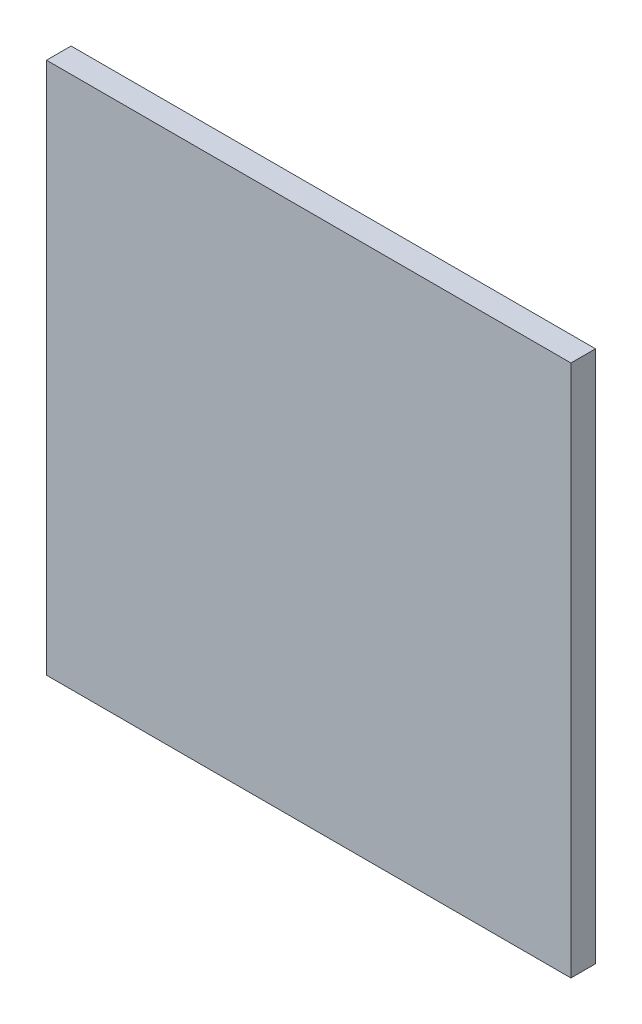
SolidWorks part; units mm, degrees
material "Perspex (TM) GS Acrylic Cast Sheet"
ref_plane "Front Plane" through (0, 0, 0) normal (0, 0, 1) x (1, 0, 0)
ref_plane "Top Plane" through (0, 0, 0) normal (0, 1, 0) x (1, 0, 0)
ref_plane "Right Plane" through (0, 0, 0) normal (1, 0, 0) x (0, 0, -1)
sketch "Sketch1" plane through (0, 0, 0) normal (0, 0, 1) x (1, 0, 0)
  line L1 (-32, -32.5) -> (32, -32.5)
  line L2 (-32, -32.5) -> (-32, 32.5)
  line L3 (-32, 32.5) -> (32, 32.5)
  line L4 (32, -32.5) -> (32, 32.5)
  line L5 (-32, -32.5) -> (32, 32.5) construction
  line L6 (-32, 32.5) -> (32, -32.5) construction
  point P0 (0, 0)
  dimension "D1" = 64
  dimension "D2" = 65
extrude "Boss-Extrude1" add sketch "Sketch1" along normal blind 3
